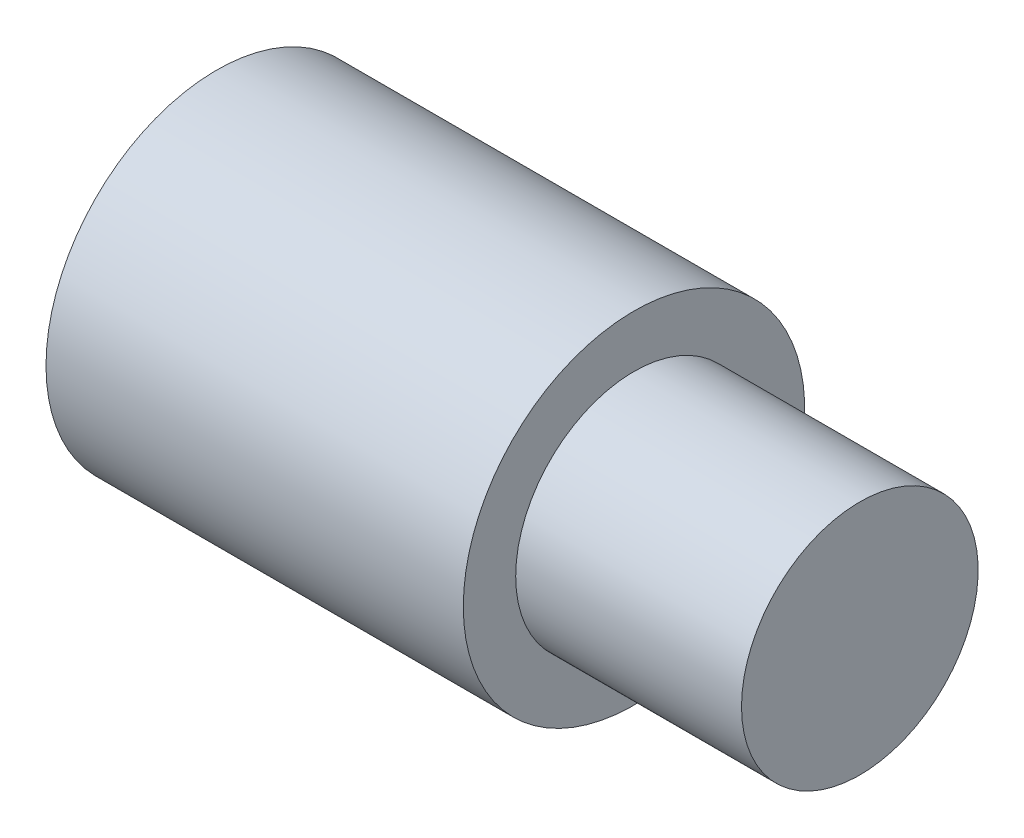
SolidWorks part; units mm, degrees
ref_plane "Front Plane" through (0, 0, 0) normal (0, 0, 1) x (1, 0, 0)
ref_plane "Top Plane" through (0, 0, 0) normal (0, 1, 0) x (1, 0, 0)
ref_plane "Right Plane" through (0, 0, 0) normal (1, 0, 0) x (0, 0, -1)
sketch "Conn_T4_ORB6 Sketch" plane through (0, 0, 0) normal (0, 0, 1) x (1, 0, 0)
  line L0 (-1000, 0) -> (1000, 0) construction
  line L1 (12.5, 0) -> (12.5, 6.55)
  line L2 (12.5, 6.55) -> (0, 6.55)
  line L3 (0, 6.55) -> (0, 9.45)
  line L4 (0, 9.45) -> (-23.1, 9.45)
  line L5 (-23.1, 9.45) -> (-23.1, 0)
  line L6 (-23.1, 0) -> (12.5, 0)
revolve "Conn_T4_ORB6" add sketch "Conn_T4_ORB6 Sketch" angle 360 about L0
ref_axis "Engine Axis" through (14.28, 0, 0) along (-1, 0, 0)
sketch "Socket Sketch" plane through (0, 0, 0) normal (0, 0, 1) x (1, 0, 0)
  line L0 (-1000, 0) -> (1000, 0) construction
  line L1 (-24.1, 0) -> (-24.1, 3.175)
  line L2 (-24.1, 3.175) -> (-7.9, 3.175)
  line L3 (-7.9, 3.175) -> (-7.9, 0)
  line L4 (-7.9, 0) -> (-24.1, 0)
revolve "Socket" cut sketch "Socket Sketch" angle 360 about L0
